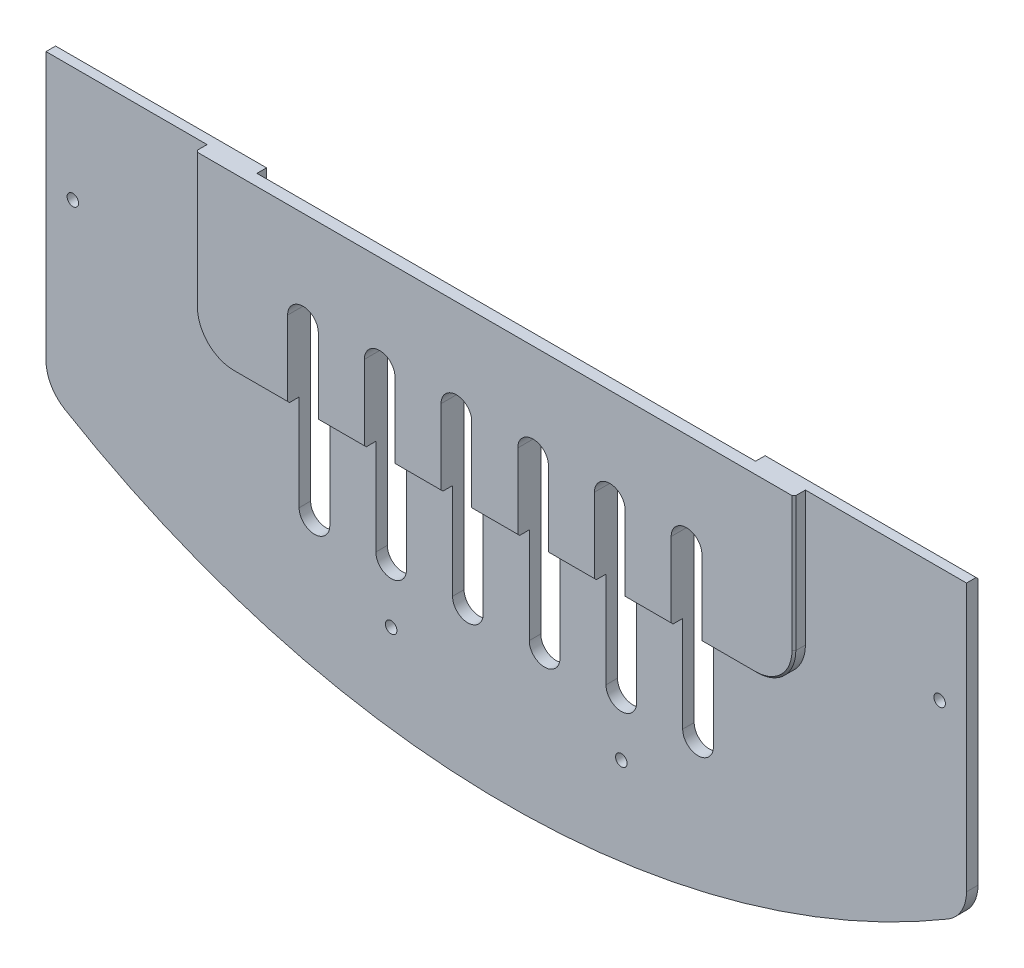
SolidWorks part; units mm, degrees
ref_plane "前视基准面" through (0, 0, 0) normal (0, 0, 1) x (1, 0, 0)
ref_plane "上视基准面" through (0, 0, 0) normal (0, 1, 0) x (1, 0, 0)
ref_plane "右视基准面" through (0, 0, 0) normal (1, 0, 0) x (0, 0, -1)
other "Configuration Table"
sketch "草图1" plane through (0, 0, 0) normal (0, 0, 1) x (1, 0, 0)
  line L1 (-120, -15) -> (120, -15)
  line L2 (-120, -15) -> (-120, -90.3287)
  line L4 (120, -15) -> (120, -90.3287)
  arc A1 (-120, -90.3287) -> (120, -90.3287) centre (0, 100) ccw
  dimension "D3" = 15
  dimension "D5" = 450
  dimension "D2" = 240
  dimension "D4" = 120
  dimension "D6" = 100
extrude "凸台-拉伸1" add sketch "草图1" along normal blind 3
sketch "草图2" plane through (0, 0, 3) normal (0, 0, 1) x (1, 0, 0)
  line L0 (120, -15) -> (-120, -15) construction
  line L1 (-78, -15) -> (78, -15)
  line L2 (-78, -15) -> (-78, -60)
  line L3 (-78, -60) -> (78, -60)
  line L4 (78, -15) -> (78, -60)
  dimension "D1" = 156
  dimension "D2" = 78
  dimension "D3" = 45
extrude "凸台-拉伸2" add sketch "草图2" along normal blind 3
sketch "草图3" plane through (0, 0, 0) normal (0, 0, -1) x (-1, 0, 0)
  line L0 (0, 0) -> (0, -50000) construction
  line L1 (-120, -15) -> (120, -15) construction
  circle A0 centre (30, -100) radius 1.5
  circle A1 centre (113, -45) radius 1.5
  circle A2 centre (-113, -45) radius 1.5
  circle A3 centre (-30, -100) radius 1.5
  dimension "D1" = 30
  dimension "D2" = 3
  dimension "D4" = 3
  dimension "D3" = 85
  dimension "D5" = 113
  dimension "D6" = 30
extrude "切除-拉伸1" cut sketch "草图3" against normal blind 3
sketch "草图4" plane through (0, 0, 0) normal (0, 0, -1) x (-1, 0, 0)
  line L0 (-120, -15) -> (120, -15) construction
  line L1 (-65, -15) -> (65, -15)
  line L2 (-65, -15) -> (-65, -35)
  line L3 (-65, -35) -> (65, -35)
  line L4 (65, -15) -> (65, -35)
  dimension "D1" = 130
  dimension "D2" = 65
  dimension "D3" = 20
extrude "切除-拉伸2" cut sketch "草图4" against normal blind 3
fillet "圆角1" radius 10 2 edges at (120, -90.3287, 1.5) (-120, -90.3287, 1.5)
chamfer "倒角1" distance 0.5 angle 45 5 edges at (92.5, -15, 0) (-92.5, -15, 0) (-65, -25, 0) (65, -25, 0) (0, -35, 0)
fillet "圆角2" radius 10 2 edges at (-78, -60, 4.5) (78, -60, 4.5)
chamfer "倒角2" distance 0.5 angle 45 5 edges at (78, -32.5, 6) (75.0711, -57.0711, 6) (-78, -32.5, 6) (0, -60, 6) (-75.0711, -57.0711, 6)
sketch "草图5" plane through (0, 0, 0) normal (0, 0, -1) x (-1, 0, 0)
  line L0 (-50, -40) -> (-50, -85) construction
  line L1 (-46, -40) -> (-46, -85)
  line L2 (-54, -40) -> (-54, -85)
  line L3 (-30, -40) -> (-30, -85) construction
  line L4 (-26, -40) -> (-26, -85)
  line L5 (-34, -40) -> (-34, -85)
  line L6 (-10, -40) -> (-10, -85) construction
  line L7 (-6, -40) -> (-6, -85)
  line L8 (-14, -40) -> (-14, -85)
  line L9 (0, 0) -> (0, -50000) construction
  line L10 (10, -40) -> (10, -85) construction
  line L11 (6, -40) -> (6, -85)
  line L12 (14, -40) -> (14, -85)
  line L13 (30, -40) -> (30, -85) construction
  line L14 (26, -40) -> (26, -85)
  line L15 (34, -40) -> (34, -85)
  line L16 (50, -40) -> (50, -85) construction
  line L17 (46, -40) -> (46, -85)
  line L18 (54, -40) -> (54, -85)
  arc A0 (-46, -40) -> (-54, -40) centre (-50, -40) ccw
  arc A1 (-54, -85) -> (-46, -85) centre (-50, -85) ccw
  arc A2 (-26, -40) -> (-34, -40) centre (-30, -40) ccw
  arc A3 (-34, -85) -> (-26, -85) centre (-30, -85) ccw
  arc A4 (-6, -40) -> (-14, -40) centre (-10, -40) ccw
  arc A5 (-14, -85) -> (-6, -85) centre (-10, -85) ccw
  arc A6 (6, -40) -> (14, -40) centre (10, -40) cw
  arc A7 (14, -85) -> (6, -85) centre (10, -85) cw
  arc A8 (26, -40) -> (34, -40) centre (30, -40) cw
  arc A9 (34, -85) -> (26, -85) centre (30, -85) cw
  arc A10 (46, -40) -> (54, -40) centre (50, -40) cw
  arc A11 (54, -85) -> (46, -85) centre (50, -85) cw
  point P2 (-50, -62.5)
  point P7 (-30, -62.5)
  point P14 (-10, -62.5)
  point P26 (10, -62.5)
  point P33 (30, -62.5)
  point P40 (50, -62.5)
  point P45 (0, 0)
  dimension "D4" = 4
  dimension "D5" = 4
  dimension "D6" = 4
  dimension "D1" = 20
  dimension "D2" = 20
  dimension "D3" = 20
  dimension "D7" = 85
  dimension "D8" = 45
extrude "切除-拉伸3" cut sketch "草图5" against normal blind 10
